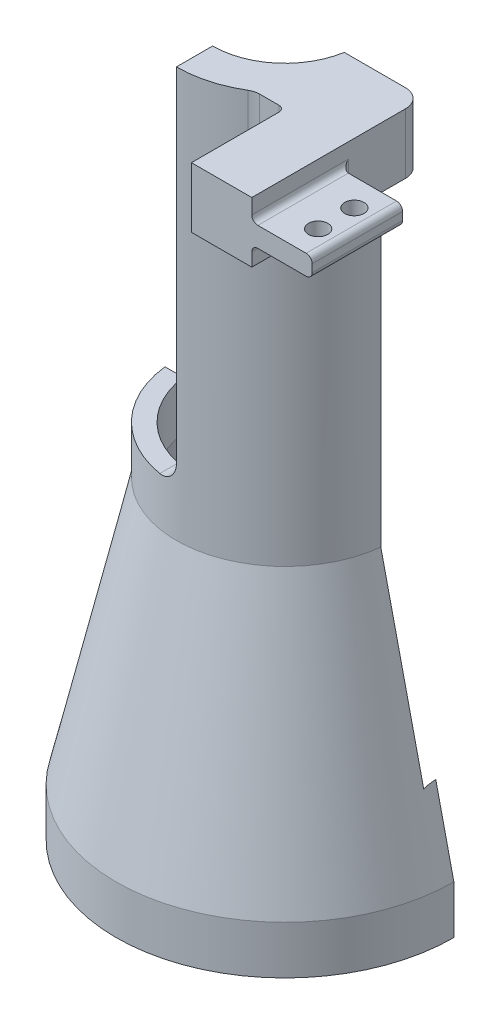
SolidWorks part; units mm, degrees
ref_plane "前视基准面" through (0, 0, 0) normal (0, 0, 1) x (1, 0, 0)
ref_plane "上视基准面" through (0, 0, 0) normal (0, 1, 0) x (1, 0, 0)
ref_plane "右视基准面" through (0, 0, 0) normal (1, 0, 0) x (0, 0, -1)
sketch "草图1" plane through (0, 0, 0) normal (0, 0, 1) x (1, 0, 0)
  line L0 (6.6106, -8) -> (9.6106, -8)
  line L1 (6.6106, 0) -> (12.6106, 0)
  line L4 (12.6106, 0) -> (12.6106, -8)
  line L7 (19.6106, -60) -> (22.6106, -60)
  line L8 (22.6106, -52) -> (22.6106, -60)
  line L9 (12.6106, -8) -> (22.6106, -52)
  line L13 (6.6106, 0) -> (-5.3894, 0)
  line L14 (6.6106, -8) -> (6.6106, -60)
  line L15 (6.6106, -60) -> (-5.3894, -60)
  line L16 (-5.3894, 0) -> (-5.3894, -60)
  line L18 (9.6106, -8) -> (19.6106, -52)
  line L19 (19.6106, -52) -> (19.6106, -60)
  dimension "D1" = 6
  dimension "D2" = 8
  dimension "D3" = 12
  dimension "D4" = 8
revolve "旋转2" add sketch "草图1" angle 180 about L16
sketch "草图2" plane through (0, 0, 0) normal (0, 1, 0) x (1, 0, 0)
  line L0 (-23.3894, 0) -> (12.6106, 0) construction
  circle A0 centre (-5.3894, 0) radius 15
extrude "切除-拉伸2" cut sketch "草图2" against normal blind 60
sketch "草图3" plane through (0, 0, 0) normal (0, 1, 0) x (1, 0, 0)
  line L2 (-5.3894, -15) -> (-5.3894, -18)
  line L3 (9.6106, 0) -> (12.6106, 0)
  arc A0 (-5.3894, -15) -> (9.6106, 0) centre (-5.3894, 0) ccw
  arc A2 (-5.3894, -18) -> (12.6106, 0) centre (-5.3894, 0) ccw
extrude "凸台-拉伸1" add sketch "草图3" along normal blind 60
sketch "草图4" plane through (0, 60, 0) normal (0, 1, 0) x (1, 0, 0)
  line L1 (6.6106, 0) -> (29.6106, 0)
  line L2 (-5.3894, -12) -> (-5.3894, -15)
  line L3 (-5.3894, -15) -> (29.6106, -15)
  line L4 (29.6106, 0) -> (29.6106, -15)
  arc A1 (-5.3894, -12) -> (6.6106, 0) centre (-5.3894, 0) ccw
  dimension "D1" = 15
  dimension "D2" = 35
extrude "凸台-拉伸2" add sketch "草图4" against normal blind 10
sketch "草图8" plane through (0, 0, 15) normal (0, 0, 1) x (1, 0, 0)
  line L0 (4.5605, 50) -> (29.6106, 50) construction
  line L1 (29.6106, 60) -> (9.6106, 60)
  line L2 (29.6106, 60) -> (29.6106, 50)
  line L3 (29.6106, 50) -> (9.6106, 50)
  line L4 (9.6106, 60) -> (9.6106, 50)
  dimension "D1" = 20
extrude "凸台-拉伸3" add sketch "草图8" along normal blind 15.5
sketch "草图9" plane through (29.6106, 0, 0) normal (1, 0, 0) x (0, 0, -1)
  line L1 (-30.5, 60) -> (-15.5, 60)
  line L2 (-30.5, 60) -> (-30.5, 56.5)
  line L3 (-30.5, 56.5) -> (-15.5, 56.5)
  line L4 (-15.5, 60) -> (-15.5, 56.5)
  line L5 (-30.5, 50) -> (-15.5, 50)
  line L6 (-30.5, 50) -> (-30.5, 53.2)
  line L7 (-30.5, 53.2) -> (-15.5, 53.2)
  line L8 (-15.5, 50) -> (-15.5, 53.2)
  dimension "D1" = 15
  dimension "D2" = 15
  dimension "D3" = 3.3
  dimension "D4" = 3.5
extrude "切除-拉伸5" cut sketch "草图9" against normal blind 10
sketch "草图10" plane through (0, 56.5, 0) normal (0, 1, 0) x (1, 0, 0)
  line L0 (29.6106, -30.5) -> (29.6106, -15.5) construction
  line L1 (19.6106, -15.5) -> (29.6106, -15.5) construction
  line L2 (19.6106, -30.5) -> (29.6106, -30.5) construction
  circle A0 centre (26.1106, -26) radius 1.6
  circle A1 centre (26.1106, -20) radius 1.6
  dimension "D1" = 3.5
  dimension "D2" = 4.5
  dimension "D3" = 3.5
  dimension "D4" = 4.5
extrude "切除-拉伸6" cut sketch "草图10" against normal blind 10
fillet "圆角10" radius 1 5 edges at (29.6106, 53.2, 23) (29.6106, 56.5, 23) (19.6106, 53.2, 23) (19.6106, 56.5, 23) (9.6106, 55, 15)
sketch "草图12" plane through (0, 60, 0) normal (0, 1, 0) x (1, 0, 0)
  line L1 (19.6106, -15.5) -> (29.6106, -15.5)
  line L2 (19.6106, -15.5) -> (19.6106, 0)
  line L3 (19.6106, 0) -> (29.6106, 0)
  line L4 (29.6106, -15.5) -> (29.6106, 0)
extrude "切除-拉伸8" cut sketch "草图12" against normal blind 10
fillet "圆角11" radius 1 1 edges at (19.6106, 54.85, 15.5)
sketch "草图13" plane through (0, 60, 0) normal (0, 1, 0) x (1, 0, 0)
  line L1 (19.6106, 0) -> (-36.0678, 0)
  line L2 (19.6106, 0) -> (19.6106, -2)
  line L3 (19.6106, -2) -> (-36.0678, -2)
  line L4 (-36.0678, 0) -> (-36.0678, -2)
  dimension "D1" = 2
extrude "切除-拉伸9" cut sketch "草图13" against normal blind 150
fillet "圆角12" radius 3 4 edges at (4.5605, 55, 15) (9.9727, 50, 9.3811) (4.4848, 50, 11.2916) (19.6106, 55, 2)
fillet "圆角13" radius 3 1 edges at (-5.3894, 0, 16.5)
